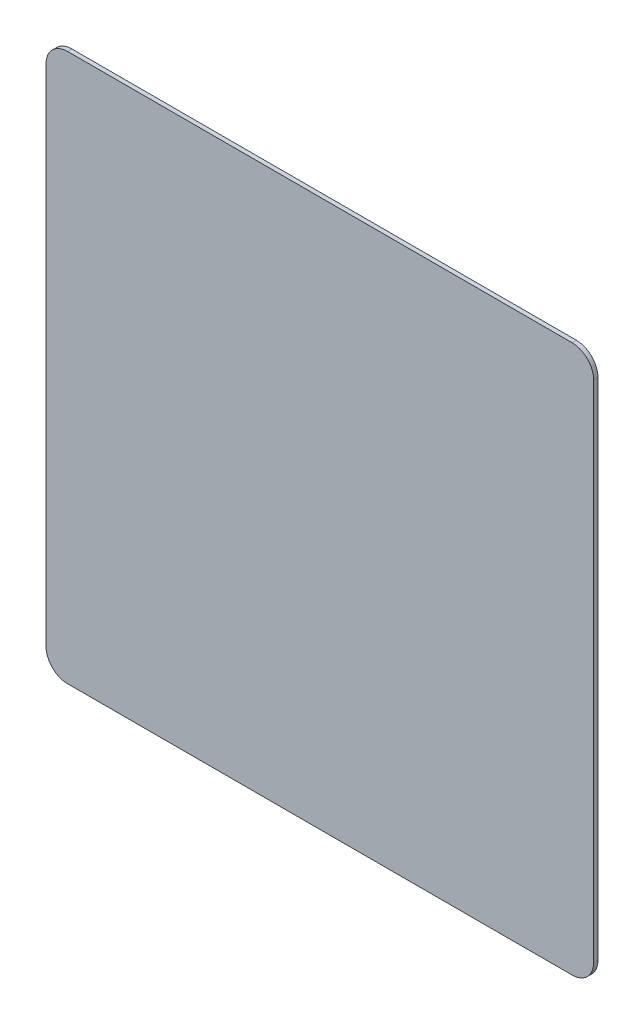
SolidWorks part; units mm, degrees
material "Acrylic (Medium-high impact)"
ref_plane "Front Plane" through (0, 0, 0) normal (0, 0, 1) x (1, 0, 0)
ref_plane "Top Plane" through (0, 0, 0) normal (0, 1, 0) x (1, 0, 0)
ref_plane "Right Plane" through (0, 0, 0) normal (1, 0, 0) x (0, 0, -1)
sketch "Sketch1" plane through (0, 0, 0) normal (0, 0, 1) x (1, 0, 0)
  line L1 (-255, 255) -> (255, 255)
  line L2 (-255, 255) -> (-255, -255)
  line L3 (-255, -255) -> (255, -255)
  line L4 (255, 255) -> (255, -255)
  line L5 (-255, 255) -> (255, -255) construction
  line L6 (-255, -255) -> (255, 255) construction
  dimension "D1" = 510
extrude "Boss-Extrude1" add sketch "Sketch1" along normal blind 4
fillet "Fillet1" radius 20 4 edges at (255, -255, 2) (-255, -255, 2) (-255, 255, 2) (255, 255, 2)
